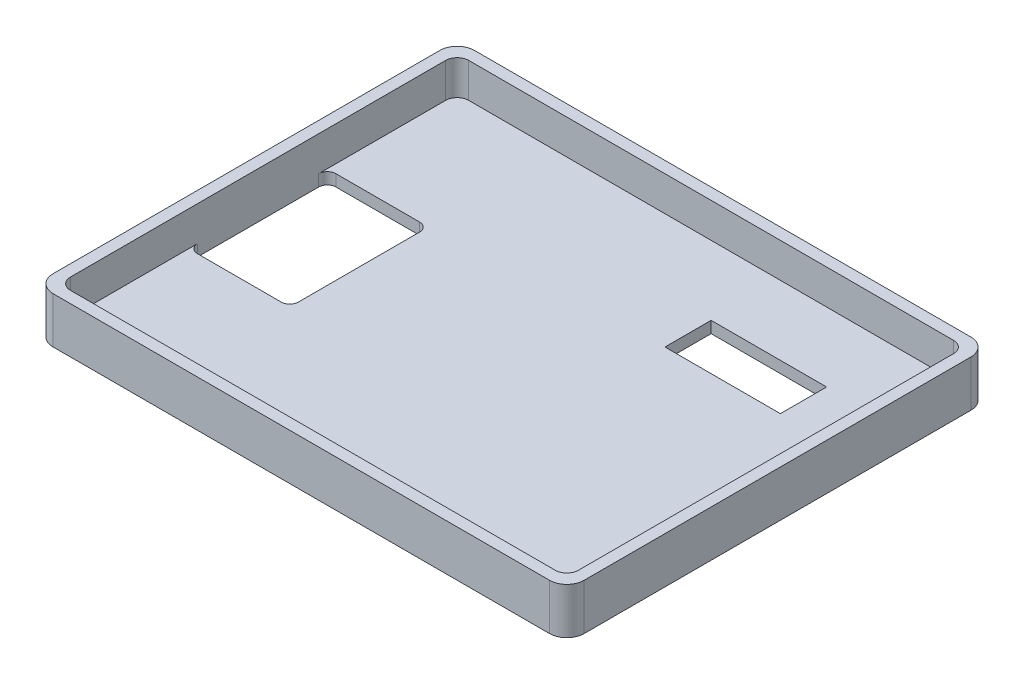
SolidWorks part; units mm, degrees
ref_plane "Front Plane" through (0, 0, 0) normal (0, 0, 1) x (1, 0, 0)
ref_plane "Top Plane" through (0, 0, 0) normal (0, 1, 0) x (1, 0, 0)
ref_plane "Right Plane" through (0, 0, 0) normal (1, 0, 0) x (0, 0, -1)
sketch "Sketch1" plane through (0, 0, 0) normal (0, 1, 0) x (1, 0, 0)
  line L0 (0, 17.25) -> (44, 17.25) construction
  line L1 (1, 0) -> (43, 0)
  line L2 (0, 12) -> (0, 22.5)
  line L3 (1, 34.5) -> (43, 34.5)
  line L4 (44, 1) -> (44, 33.5)
  line L5 (0.5, -1) -> (43.5, -1)
  line L6 (-1, 0.5) -> (-1, 34)
  line L7 (0.5, 35.5) -> (43.5, 35.5)
  line L8 (45, 0.5) -> (45, 34)
  line L9 (0.75, 24) -> (8.25, 24)
  line L10 (8, 23.25) -> (0.75, 23.25)
  line L11 (8.75, 22.5) -> (8.75, 12)
  line L12 (8, 11.25) -> (0.75, 11.25)
  line L13 (0, 1) -> (0, 9.75)
  line L14 (0, 24.75) -> (0, 33.5)
  line L15 (0, 24.75) -> (0, 22.5)
  line L16 (9.5, 22.75) -> (9.5, 11.75)
  line L17 (8.25, 10.5) -> (0.75, 10.5)
  line L18 (0, 12) -> (0, 9.75)
  line L26 (28, 28.5) -> (38, 28.5)
  line L27 (28, 28.5) -> (28, 24.5)
  line L28 (28, 24.5) -> (38, 24.5)
  line L29 (38, 28.5) -> (38, 24.5)
  arc A0 (0, 1) -> (1, 0) centre (1, 1) ccw
  arc A1 (43, 0) -> (44, 1) centre (43, 1) ccw
  arc A2 (44, 33.5) -> (43, 34.5) centre (43, 33.5) ccw
  arc A3 (1, 34.5) -> (0, 33.5) centre (1, 33.5) ccw
  arc A4 (0.5, -1) -> (-1, 0.5) centre (0.5, 0.5) cw
  arc A5 (-1, 34) -> (0.5, 35.5) centre (0.5, 34) cw
  arc A6 (43.5, -1) -> (45, 0.5) centre (43.5, 0.5) ccw
  arc A7 (43.5, 35.5) -> (45, 34) centre (43.5, 34) cw
  arc A8 (9.5, 11.75) -> (8.25, 10.5) centre (8.25, 11.75) cw
  arc A9 (9.5, 22.75) -> (8.25, 24) centre (8.25, 22.75) ccw
  arc A10 (0.75, 23.25) -> (0, 22.5) centre (0.75, 22.5) ccw
  arc A11 (0, 12) -> (0.75, 11.25) centre (0.75, 12) ccw
  arc A12 (8.75, 12) -> (8, 11.25) centre (8, 12) cw
  arc A13 (8, 23.25) -> (8.75, 22.5) centre (8, 22.5) cw
  arc A14 (0.75, 24) -> (0, 24.75) centre (0.75, 24.75) cw
  arc A15 (0.75, 10.5) -> (0, 9.75) centre (0.75, 9.75) ccw
  point P7 (0, 0)
  point P10 (44, 0)
  point P13 (44, 34.5)
  point P22 (-1, -1)
  point P27 (45, -1)
  point P30 (45, 35.5)
  point P33 (4, 17.25)
  point P36 (0, 24)
  point P44 (9.5, 10.5)
  point P47 (9.5, 24)
  point P61 (0, 10.5)
  dimension "D3" = 0.75
  dimension "D6" = 10
  dimension "D5" = 6
  dimension "D2" = 0.75
  dimension "D1" = 7.25
  dimension "D4" = 0.75
  dimension "D7" = 4
  dimension "D8" = 6
extrude "Boss-Extrude1" add sketch "Sketch1" along normal blind 1 contours L17 A15 L13 A0 L1 A1 L4 A2 L3 A3 L14 A14 L9 A9 L16 A8 | A15 L17 A8 L16 A9 L9 A14 L15 A10 L10 A13 L11 A12 L12 A11 L18 | L11 L0 L16 A9 L9 A14 L15 A10 L10 A13 | L16 L0 L4 A2 L3 A3 L14 A14 L9 A9 L26 L29 L28 L27 region at (8.871, 0, -19.875) region at (9.125, 0, -17.129) region at (23.015, 0, -26.3448) region at (23.59, 0, -8.1463)
extrude "Boss-Extrude2" add sketch "Sketch1<3>" along normal blind 4 contours A7 L7 A5 L6 A4 L5 A6 L8 A3 L3 A2 L4 A1 L1 A0 L13 L18 L2 L15 L14 region at (-0.1454, 0, 0.1454)
sketch "Sketch1<3>" plane through (0, 0, 0) normal (0, 1, 0) x (1, 0, 0) same geometry as "Sketch1"
